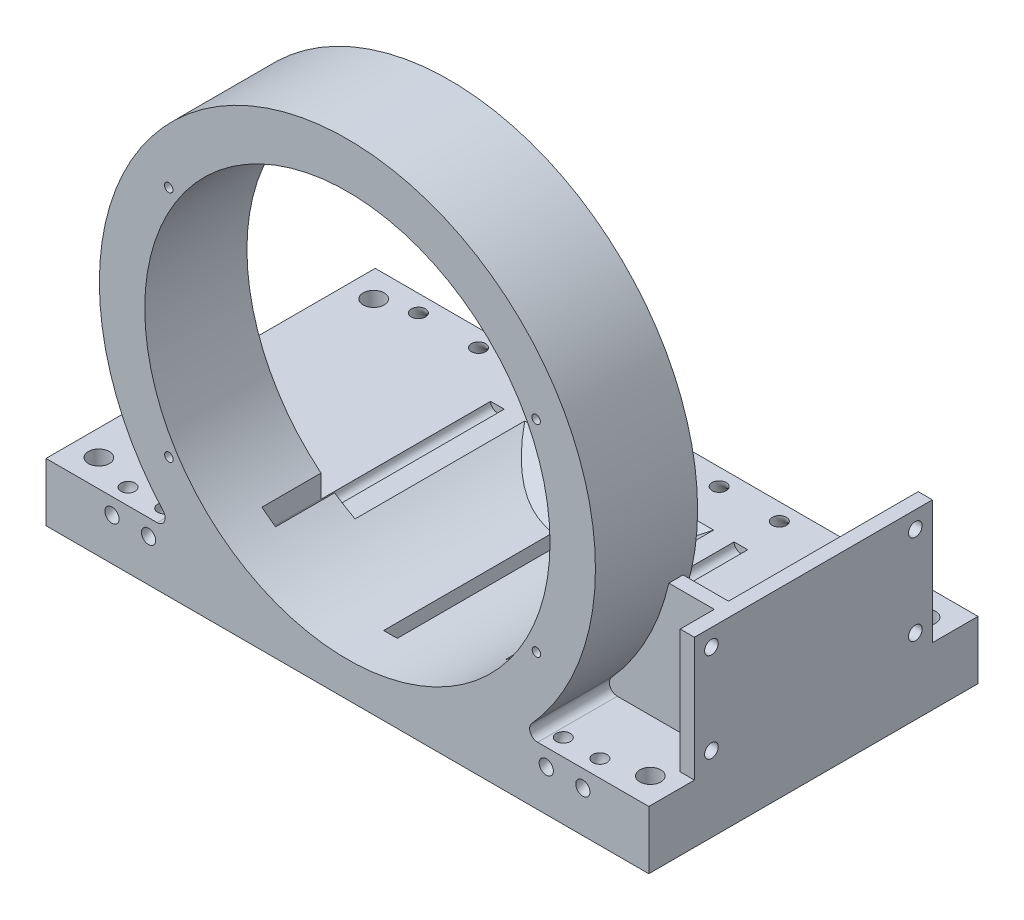
SolidWorks part; units mm, degrees
ref_plane "Front Plane" through (0, 0, 0) normal (0, 0, 1) x (1, 0, 0)
ref_plane "Top Plane" through (0, 0, 0) normal (0, 1, 0) x (1, 0, 0)
ref_plane "Right Plane" through (0, 0, 0) normal (1, 0, 0) x (0, 0, -1)
sketch "Sketch1" plane through (0, 0, 0) normal (0, 0, 1) x (1, 0, 0)
  line L0 (-34.1117, 43.7782) -> (34.1117, 43.7782)
  line L4 (28.448, -40.0843) -> (28.448, -35.2709)
  line L5 (-67.4363, -40.1112) -> (-38.3566, -40.1112)
  line L6 (-67.4363, -40.1112) -> (-67.4363, -53.1541)
  line L7 (-67.4363, -53.1541) -> (67.4363, -53.1541)
  line L8 (67.4363, -40.1112) -> (67.4363, -53.1541)
  line L9 (1.2065, -45.2975) -> (1.2065, -49.1871)
  line L10 (-1.2065, -45.2975) -> (-1.2065, -49.1871)
  line L11 (-45.339, 0) -> (45.339, 0) construction
  line L12 (-28.448, -35.2709) -> (-28.448, -40.0843)
  line L13 (38.3566, -40.1112) -> (67.4363, -40.1112)
  line L14 (26.035, -37.0877) -> (26.035, -40.0843)
  line L15 (0, 45.339) -> (0, -45.339) construction
  line L16 (-26.035, -40.0843) -> (-26.035, -37.0877)
  line L17 (-39.989, 26.0985) -> (-39.9308, -26.0985) construction
  line L18 (42.2197, 22.3102) -> (42.298, -22.7748) construction
  arc A1 (-26.035, -37.1188) -> (-1.2065, -45.3229) centre (0, 0) ccw
  arc A2 (-34.1117, 43.7782) -> (-38.3566, -40.1112) centre (0, 0) ccw
  circle A3 centre (-39.989, 26.0985) radius 0.9525
  arc A4 (38.3566, -40.1112) -> (34.1117, 43.7782) centre (0, 0) ccw
  circle A5 centre (-39.9308, -26.0985) radius 0.9525
  circle A6 centre (42.298, -22.7748) radius 0.9525
  circle A7 centre (42.2197, 22.3102) radius 0.9525
  arc A9 (-1.2065, -49.1871) -> (1.2065, -49.1871) centre (0, -49.1871) ccw
  arc A10 (-28.448, -40.0843) -> (-26.035, -40.0843) centre (-27.2415, -40.0843) ccw
  arc A11 (1.2065, -45.3229) -> (26.035, -37.1188) centre (0, 0) ccw
  arc A12 (26.035, -40.0843) -> (28.448, -40.0843) centre (27.2415, -40.0843) ccw
  arc A13 (28.448, -35.3035) -> (-28.448, -35.3035) centre (0, 0) ccw
  point P8 (0, -45.339)
  point P24 (-39.9599, 0)
  point P25 (42.2589, -0.2323)
  dimension "D1" = 90.678
  dimension "D2" = 10.16
  dimension "D4" = 1.905
  dimension "D5" = 1.905
  dimension "D6" = 1.905
  dimension "D7" = 1.905
  dimension "D10" = 82.296
  dimension "D3" = 2.413
  dimension "D8" = 52.197
  dimension "D9" = 45.085
  dimension "D11" = 82.296
  dimension "D12" = 47.752
  dimension "D13" = 47.752
extrude "Boss-Extrude1" add sketch "Sketch1" along normal blind 22.86 contours L13 A4 L0 A1 A2 L5 L6 L7 L8 region at (-22.9528, 42.1173, 0)
sketch "Sketch2" plane through (0, 0, 0) normal (0, 0, -1) x (-1, 0, 0)
  line L0 (21.1356, -40.1112) -> (26.0353, -40.1112)
  line L1 (-67.4363, -53.1541) -> (67.4363, -53.1541)
  line L2 (-67.4363, -53.1541) -> (-67.4363, -40.1112)
  line L3 (-67.4363, -40.1112) -> (-28.4477, -40.1112)
  line L4 (67.4363, -53.1541) -> (67.4363, -40.1112)
  line L5 (1.2065, -49.1871) -> (1.2065, -45.3229)
  line L6 (28.4477, -40.1112) -> (67.4363, -40.1112)
  line L7 (-1.2065, -45.3229) -> (-1.2065, -49.1871)
  line L8 (-26.0353, -40.1112) -> (-21.1356, -40.1112)
  arc A0 (-21.1356, -40.1112) -> (-1.2065, -45.3229) centre (0, 0) ccw
  arc A1 (-28.4477, -40.1112) -> (-26.0353, -40.1112) centre (-27.2415, -40.0843) ccw
  arc A2 (-1.2065, -49.1871) -> (1.2065, -49.1871) centre (0, -49.1871) ccw
  arc A3 (26.0353, -40.1112) -> (28.4477, -40.1112) centre (27.2415, -40.0843) ccw
  arc A4 (1.2065, -45.3229) -> (21.1356, -40.1112) centre (0, 0) ccw
extrude "Boss-Extrude2" add sketch "Sketch2" along normal blind 50.8 contours L2 L3 A1 L8 A0 L7 A2 L5 A4 L0 A3 L6 L4 L1
sketch "Sketch3" plane through (0, 0, 0) normal (0, 0, -1) x (-1, 0, 0)
  line L0 (-28.448, 40.2554) -> (-28.448, 35.2709)
  line L1 (-28.448, 35.2709) -> (-26.035, 37.0877)
  line L2 (-26.035, 37.0877) -> (-26.035, 40.2554)
  line L3 (28.448, 40.2554) -> (28.448, 35.3035)
  line L4 (28.448, 35.3035) -> (26.0792, 37.0877)
  line L5 (26.0792, 37.0877) -> (26.035, 40.2554)
  line L6 (-25.7175, 36.9294) -> (-25.7175, 40.2554)
  line L7 (-28.7655, 40.2554) -> (-28.7655, 34.6344)
  line L8 (-28.7655, 34.6344) -> (-25.7175, 36.9294)
  line L9 (25.7639, 36.9278) -> (25.7175, 40.251)
  line L10 (28.7655, 34.6668) -> (25.7639, 36.9278)
  line L11 (28.7655, 40.2554) -> (28.7655, 34.6668)
  arc A0 (-26.035, 40.2554) -> (-28.448, 40.2554) centre (-27.2415, 40.2554) ccw
  arc A1 (28.448, 40.2554) -> (26.0355, 40.2217) centre (27.2415, 40.2554) ccw
  arc A2 (28.448, -35.3035) -> (11.7939, 43.7782) centre (0, 0) ccw construction
  arc A3 (-25.7175, 40.2554) -> (-28.7655, 40.2554) centre (-27.2415, 40.2554) ccw
  arc A4 (28.7655, 40.2554) -> (25.7181, 40.2129) centre (27.2415, 40.2554) ccw
  arc M5 (11.7939, 43.7782) -> (28.448, -35.3035) centre (0, 0) cw
  dimension "D1" = 0.3175
extrude "Cut-Extrude1" cut sketch "Sketch3" against normal blind 13.208 contours L3 A1 L5 M5 | L2 A0 L0 L1 region at (27.3142, 38.671, 0) region at (-27.3223, 38.7004, 0)
sketch "Sketch4" plane through (0, 0, 22.86) normal (0, 0, 1) x (1, 0, 0)
  line L0 (-26.035, -40.0843) -> (-26.035, -37.1188)
  line L2 (-28.448, -35.3035) -> (-28.448, -40.0843)
  line L3 (-1.2065, -45.3229) -> (-1.2065, -49.1871)
  line L5 (1.2065, -45.2975) -> (1.2065, -49.1871)
  line L6 (28.448, -40.0843) -> (28.448, -35.3035)
  line L7 (1.1905, -45.3234) -> (1.2065, -45.2975)
  line L8 (26.035, -37.1188) -> (26.035, -40.0843)
  arc A0 (-28.448, -40.0843) -> (-26.035, -40.0843) centre (-27.2415, -40.0843) ccw
  arc A1 (-1.2065, -49.1871) -> (1.2065, -49.1871) centre (0, -49.1871) ccw
  arc A2 (26.035, -40.0843) -> (28.448, -40.0843) centre (27.2415, -40.0843) ccw
  arc A3 (-28.448, -35.3035) -> (-26.035, -37.1188) centre (0, 0) ccw
  arc A4 (-1.2065, -45.3229) -> (1.2065, -45.3229) centre (0, 0) ccw
  arc A5 (26.035, -37.1188) -> (28.448, -35.3035) centre (0, 0) ccw
  line M14 (28.448, -35.3035) -> (28.448, -40.0843)
  arc M15 (28.448, -40.0843) -> (26.035, -40.0843) centre (27.2415, -40.0843) cw
  line M16 (26.035, -40.0843) -> (26.035, -37.1188)
  line M18 (1.2065, -45.3229) -> (1.2065, -49.1871)
  arc M19 (1.2065, -49.1871) -> (-1.2065, -49.1871) centre (0, -49.1871) cw
  line M20 (-1.2065, -49.1871) -> (-1.2065, -45.3229)
  line M22 (-26.035, -37.1188) -> (-26.035, -40.0843)
  arc M23 (-26.035, -40.0843) -> (-28.448, -40.0843) centre (-27.2415, -40.0843) cw
  line M24 (-28.448, -40.0843) -> (-28.448, -35.3035)
extrude "Boss-Extrude3" add sketch "Sketch4" against normal blind 9.652 contours A3 M24 M23 M22 | A4 M20 M19 M18 | A5 M16 M15 M14 region at (-27.3175, -38.611, 22.86) region at (0, -47.7417, 22.86) region at (27.3175, -38.611, 22.86)
sketch "Sketch6" plane through (67.4363, 0, 0) normal (1, 0, 0) x (0, 0, -1)
  line L2 (20.8189, -46.8236) -> (20.8189, -53.1541)
  line L3 (50.8, -40.1112) -> (50.8, -45.3976)
  line L5 (-22.86, -53.1541) -> (50.8, -53.1541) construction
  line L6 (20.8189, -53.1541) -> (50.8, -53.1541)
  line L9 (50.8, -53.1541) -> (50.8, -45.3976)
  line L10 (50.8, -53.1541) -> (50.8, -40.1112) construction
  line L12 (50.8, -40.1112) -> (37.9477, -40.1112)
  line L13 (-22.86, -40.1112) -> (50.8, -40.1112) construction
  line L14 (37.9477, -40.1112) -> (20.8189, -46.8236)
extrude "Boss-Extrude5" add sketch "Sketch6" against normal blind 116.84 contours L14 L2 L6 L9 L3 L12
sketch "Sketch7" plane through (0, -53.1541, 0) normal (0, -1, 0) x (1, 0, 0)
  line L0 (-61.6911, -44.7061) -> (-61.6911, 16.7661) construction
  line L1 (0, -13.97) -> (-61.6911, 16.7661)
  line L2 (-61.6911, 16.7661) -> (61.6911, -44.7061)
  line L3 (0, -13.97) -> (-61.6911, -13.97) construction
  line L4 (0, 22.86) -> (0, -50.8) construction
  line L5 (-67.4363, 22.86) -> (67.4363, 22.86) construction
  line L6 (67.4363, -50.8) -> (-67.4363, -50.8) construction
  circle A0 centre (-61.6911, 16.7661) radius 2.3495
  circle A1 centre (61.6911, -44.7061) radius 2.3495
  circle A2 centre (-61.6911, -44.7061) radius 2.3495
  circle A3 centre (61.6911, 16.7661) radius 2.3495
  dimension "D3" = 4.699
  dimension "D4" = 4.699
  dimension "D1" = 68.9238
  dimension "D2" = 137.8477
  dimension "D5" = 61.4723
extrude "Cut-Extrude2" cut sketch "Sketch7" against normal blind 25.4 contours A0 | A2 | A1 | A3 region at (-63.9134, -53.1541, 17.2891) region at (-61.6911, -53.1541, -44.7061)
sketch "Sketch8" plane through (0, -40.1112, 0) normal (0, 1, 0) x (1, 0, 0)
  line L0 (-67.4363, 50.8) -> (67.4363, 50.8)
  line L1 (-67.4363, 50.8) -> (-67.4363, 46.99)
  line L2 (-67.4363, -22.86) -> (-67.4363, 50.8) construction
  line L3 (-67.4363, 46.99) -> (67.4363, 46.99) construction
  line L4 (67.4363, -22.86) -> (67.4363, 50.8) construction
  line L5 (-67.4363, -22.86) -> (-67.4363, -17.78)
  line L6 (-67.4363, -17.78) -> (67.4363, -17.78) construction
  line L7 (-0.1263, 46.99) -> (0, -17.78) construction
  circle A0 centre (-53.9743, 46.99) radius 1.5875
  circle A1 centre (-40.5123, 46.99) radius 1.5875
  circle A2 centre (-27.0503, 46.99) radius 1.5875
  circle A3 centre (-13.5883, 46.99) radius 1.5875
  circle A4 centre (-0.1263, 46.99) radius 1.5875
  circle A5 centre (13.3357, 46.99) radius 1.5875
  circle A6 centre (26.7977, 46.99) radius 1.5875
  circle A7 centre (40.2597, 46.99) radius 1.5875
  circle A8 centre (53.7217, 46.99) radius 1.5875
  circle A9 centre (53.7217, -17.78) radius 1.5875
  circle A10 centre (44.6271, -17.78) radius 1.5875
  circle A11 centre (-53.7213, -17.9895) radius 1.5875
  circle A12 centre (-44.6267, -17.9541) radius 1.5875
  dimension "D1" = 3.175
  dimension "D6" = 3.175
  dimension "D7" = 3.175
  dimension "D2" = 3.81
  dimension "D3" = 13.462
  dimension "D5" = 5.08
  dimension "D4" = 9
revolve "Cut-Revolve1" cut sketch "Sketch8" angle 360 about L0 region at (-53.9743, -40.1112, -46.99) region at (-40.5123, -40.1112, -46.99) region at (-27.0503, -40.1112, -46.99) region at (-13.5883, -40.1112, -46.99) region at (-0.1263, -40.1112, -46.99) region at (13.3357, -40.1112, -46.99) region at (26.7977, -40.1112, -46.99) region at (40.2597, -40.1112, -46.99) region at (53.7217, -40.1112, -46.99)
sketch "Sketch9" plane through (0, -40.1112, 0) normal (0, 1, 0) x (1, 0, 0)
  line L0 (-67.4363, -22.86) -> (-67.4363, -19.05)
  line L1 (-67.4363, -22.86) -> (-67.4363, 50.8) construction
  line L2 (-67.4363, -19.05) -> (67.4363, -19.05) construction
  line L3 (67.4363, -22.86) -> (67.4363, 50.8) construction
  line L4 (0, -19.05) -> (-0.1263, 45.4025)
  circle A0 centre (44.4978, -19.05) radius 1.5875
  circle A1 centre (52.6808, -19.05) radius 1.5875
  circle A2 centre (-0.1263, 46.99) radius 1.5875 construction
  circle A3 centre (-52.6804, -19.2565) radius 1.5875
  circle A4 centre (-44.4975, -19.2244) radius 1.5875
  dimension "D2" = 3.175
  dimension "D3" = 3.175
  dimension "D1" = 3.81
revolve "Cut-Revolve2" cut sketch "Sketch9" angle 360 about axis through (0, -40.1112, 22.86) along (1, 0, 0) region at (-52.6804, -40.1112, 18.4698) region at (52.6808, -40.1112, 18.3762) region at (52.6808, -40.1112, 19.7238) region at (44.4978, -40.1112, 18.3762) region at (44.4978, -40.1112, 19.7238) region at (-44.4975, -40.1112, 18.4555) region at (-44.4975, -40.1112, 19.805) region at (-52.6804, -40.1112, 19.8201)
fillet "Fillet1" radius 1.778 2 edges at (-38.3566, -40.1112, 11.43) (38.3566, -40.1112, 11.43)
sketch "Sketch11" plane through (0, 0, 0) normal (0, 0, -1) x (-1, 0, 0)
  line L1 (28.448, -35.3035) -> (28.448, -40.0843) construction
  line L2 (28.4477, -40.1112) -> (42.5584, -40.1112) construction
  line L3 (34.1117, 43.7782) -> (11.7939, 43.7782) construction
  line L5 (-26.035, 40.2554) -> (-26.035, 37.1188) construction
  line L6 (-11.7939, 43.7782) -> (-34.1117, 43.7782) construction
  line L7 (-42.5584, -40.1112) -> (-28.4477, -40.1112) construction
  line L8 (-28.448, -40.0843) -> (-28.448, -35.3035) construction
  line L9 (-28.448, 35.3035) -> (-28.448, 40.2554) construction
  line L11 (28.448, -35.3035) -> (28.448, -40.0843)
  line L12 (28.4477, -40.1112) -> (42.5584, -40.1112)
  line L13 (34.1117, 43.7782) -> (11.7939, 43.7782)
  line L15 (-26.035, 40.2554) -> (-26.035, 37.1188)
  line L16 (-11.7939, 43.7782) -> (-34.1117, 43.7782)
  line L17 (-42.5584, -40.1112) -> (-28.4477, -40.1112)
  line L18 (-28.448, -40.0843) -> (-28.448, -35.3035)
  line L19 (-28.448, 35.3035) -> (-28.448, 40.2554)
  line L20 (-28.829, 40.2554) -> (-28.829, 34.9931)
  line L21 (-25.654, 40.2554) -> (-25.654, 37.3831)
  line L22 (-11.7939, 43.7782) -> (11.7939, 43.7782)
  line L23 (0, 43.7782) -> (0, 33.6339)
  line L24 (-25.7175, -40.0843) -> (-25.7175, -36.9533)
  line L25 (-28.7655, -34.6335) -> (-28.7655, -40.0843)
  line L26 (-26.0353, -40.1112) -> (-21.1356, -40.1112)
  line L27 (-26.035, -37.1188) -> (-26.035, -40.0843)
  line L28 (-26.0353, -40.1112) -> (-21.1356, -40.1112)
  line L29 (-26.035, -37.1188) -> (-26.035, -40.0843)
  line L30 (-28.448, -35.3035) -> (-28.448, -40.0843)
  line L31 (-26.035, -40.0843) -> (-26.035, -37.1188)
  line L32 (-28.448, -35.3035) -> (-28.448, -40.0843)
  line L33 (-26.035, -40.0843) -> (-26.035, -37.1188)
  line L34 (-1.2065, -45.3229) -> (-1.2065, -49.1871)
  line L35 (1.2065, -49.1871) -> (1.2065, -45.3229)
  line L36 (-1.2065, -45.3229) -> (-1.2065, -49.1871)
  line L37 (1.2065, -49.1871) -> (1.2065, -45.3229)
  line L38 (1.524, -49.1871) -> (1.524, -44.9957)
  line L39 (-1.524, -44.9957) -> (-1.524, -49.1871)
  line L40 (1.524, -44.9957) -> (1.524, -49.1871)
  line L41 (-1.524, -49.1871) -> (-1.524, -44.9957)
  line L42 (-1.2065, -49.1871) -> (-1.2065, -45.3229)
  line L43 (1.2065, -45.3229) -> (1.2065, -49.1871)
  line L44 (26.035, -40.0843) -> (26.035, -37.1188)
  line L45 (28.448, -35.3035) -> (28.448, -40.0843)
  line L46 (26.035, -37.1188) -> (26.035, -40.0843)
  line L47 (26.0353, -40.1112) -> (21.1356, -40.1112)
  line L48 (28.7655, -34.6335) -> (28.7655, -40.0843)
  line L49 (25.7175, -40.0843) -> (25.7175, -36.9533)
  line L50 (25.654, 40.2554) -> (25.654, 37.3831)
  line L51 (28.829, 40.2554) -> (28.829, 34.9931)
  line L53 (28.448, -40.0843) -> (28.448, -35.3035)
  line L54 (42.5584, -40.1112) -> (28.4477, -40.1112)
  line L55 (11.7939, 43.7782) -> (34.1117, 43.7782)
  line L62 (28.448, 40.2554) -> (28.448, 35.3035)
  line L63 (28.448, -35.3035) -> (28.448, -40.0843)
  line L64 (28.4477, -40.1112) -> (42.5584, -40.1112)
  line L65 (34.1117, 43.7782) -> (11.7939, 43.7782)
  line L66 (26.0792, 37.0877) -> (26.035, 40.2554)
  line L68 (28.448, -35.3035) -> (28.448, -40.0843)
  line L69 (28.4477, -40.1112) -> (42.5584, -40.1112)
  line L70 (34.1117, 43.7782) -> (11.7939, 43.7782)
  arc A0 (28.448, -35.3035) -> (28.448, 35.3035) centre (0, 0) ccw construction
  arc A1 (28.4477, -40.1112) -> (28.448, -40.0843) centre (27.2415, -40.0843) ccw construction
  arc A2 (41.2373, -37.1433) -> (42.5584, -40.1112) centre (42.5584, -38.3332) ccw construction
  arc A3 (41.2373, -37.1433) -> (34.1117, 43.7782) centre (0, 0) ccw construction
  arc A4 (26.0792, 37.0877) -> (11.7939, 43.7782) centre (0, 0) ccw construction
  arc A5 (28.448, 40.2554) -> (26.035, 40.2554) centre (27.2415, 40.2554) ccw construction
  arc A6 (-26.035, 40.2554) -> (-28.448, 40.2554) centre (-27.2415, 40.2554) ccw construction
  arc A7 (-11.7939, 43.7782) -> (-26.035, 37.1188) centre (0, 0) ccw construction
  arc A8 (-34.1117, 43.7782) -> (-41.2373, -37.1433) centre (0, 0) ccw construction
  arc A9 (-42.5584, -40.1112) -> (-41.2373, -37.1433) centre (-42.5584, -38.3332) ccw construction
  arc A10 (-28.448, -40.0843) -> (-28.4477, -40.1112) centre (-27.2415, -40.0843) ccw construction
  arc A11 (-28.448, 35.3035) -> (-28.448, -35.3035) centre (0, 0) ccw construction
  arc A12 (28.448, -35.3035) -> (28.448, 35.3035) centre (0, 0) ccw
  arc A13 (28.4477, -40.1112) -> (28.448, -40.0843) centre (27.2415, -40.0843) ccw
  arc A14 (41.2373, -37.1433) -> (42.5584, -40.1112) centre (42.5584, -38.3332) ccw
  arc A15 (41.2373, -37.1433) -> (34.1117, 43.7782) centre (0, 0) ccw
  arc A16 (26.0792, 37.0877) -> (11.7939, 43.7782) centre (0, 0) ccw
  arc A18 (-26.035, 40.2554) -> (-28.448, 40.2554) centre (-27.2415, 40.2554) ccw
  arc A19 (-11.7939, 43.7782) -> (-26.035, 37.1188) centre (0, 0) ccw
  arc A20 (-34.1117, 43.7782) -> (-41.2373, -37.1433) centre (0, 0) ccw
  arc A21 (-42.5584, -40.1112) -> (-41.2373, -37.1433) centre (-42.5584, -38.3332) ccw
  arc A22 (-28.448, -40.0843) -> (-28.4477, -40.1112) centre (-27.2415, -40.0843) ccw
  arc A23 (-28.448, 35.3035) -> (-28.448, -35.3035) centre (0, 0) ccw
  circle A24 centre (-27.2415, 40.2554) radius 1.5875
  arc A25 (-28.7655, -40.0843) -> (-25.7175, -40.0843) centre (-27.2415, -40.0843) ccw
  arc A26 (-28.7655, -34.6335) -> (-25.7175, -36.9533) centre (0, 0) ccw
  arc A27 (-26.0353, -40.1112) -> (-26.035, -40.0843) centre (-27.2415, -40.0843) ccw
  arc A28 (-26.035, -37.1188) -> (-21.1356, -40.1112) centre (0, 0) ccw
  arc A29 (-26.0353, -40.1112) -> (-26.035, -40.0843) centre (-27.2415, -40.0843) ccw
  arc A30 (-26.035, -37.1188) -> (-21.1356, -40.1112) centre (0, 0) ccw
  arc A31 (-28.448, -35.3035) -> (-26.035, -37.1188) centre (0, 0) ccw
  arc A32 (-28.448, -40.0843) -> (-26.035, -40.0843) centre (-27.2415, -40.0843) ccw
  arc A33 (-28.448, -35.3035) -> (-26.035, -37.1188) centre (0, 0) ccw
  arc A34 (-28.448, -40.0843) -> (-26.035, -40.0843) centre (-27.2415, -40.0843) ccw
  arc A35 (-1.2065, -45.3229) -> (1.2065, -45.3229) centre (0, 0) ccw
  arc A36 (-1.2065, -49.1871) -> (1.2065, -49.1871) centre (0, -49.1871) ccw
  arc A37 (-1.2065, -45.3229) -> (1.2065, -45.3229) centre (0, 0) ccw
  arc A38 (-1.2065, -49.1871) -> (1.2065, -49.1871) centre (0, -49.1871) ccw
  arc A39 (-1.524, -49.1871) -> (1.524, -49.1871) centre (0, -49.1871) ccw
  arc A40 (-1.524, -44.9957) -> (1.524, -44.9957) centre (0, 0) ccw
  arc A41 (28.448, -40.0843) -> (26.035, -40.0843) centre (27.2415, -40.0843) cw
  arc A42 (28.448, -35.3035) -> (26.035, -37.1188) centre (0, 0) cw
  arc A43 (26.035, -37.1188) -> (21.1356, -40.1112) centre (0, 0) cw
  arc A44 (26.0353, -40.1112) -> (26.035, -40.0843) centre (27.2415, -40.0843) cw
  arc A45 (28.7655, -34.6335) -> (25.7175, -36.9533) centre (0, 0) cw
  arc A46 (28.7655, -40.0843) -> (25.7175, -40.0843) centre (27.2415, -40.0843) cw
  arc A48 (28.448, 35.3035) -> (28.448, -35.3035) centre (0, 0) cw
  arc A49 (28.448, -40.0843) -> (28.4477, -40.1112) centre (27.2415, -40.0843) cw
  arc A50 (42.5584, -40.1112) -> (41.2373, -37.1433) centre (42.5584, -38.3332) cw
  arc A51 (34.1117, 43.7782) -> (41.2373, -37.1433) centre (0, 0) cw
  arc A52 (11.7939, 43.7782) -> (26.035, 37.1188) centre (0, 0) cw
  arc A54 (28.829, 40.2554) -> (25.654, 40.2554) centre (27.2415, 40.2554) ccw
  circle A55 centre (0, 0) radius 45.339
  arc A60 (28.448, -35.3035) -> (28.448, 35.3035) centre (0, 0) ccw
  arc A61 (28.4477, -40.1112) -> (28.448, -40.0843) centre (27.2415, -40.0843) ccw
  arc A62 (41.2373, -37.1433) -> (42.5584, -40.1112) centre (42.5584, -38.3332) ccw
  arc A63 (41.2373, -37.1433) -> (34.1117, 43.7782) centre (0, 0) ccw
  arc A64 (26.0792, 37.0877) -> (11.7939, 43.7782) centre (0, 0) ccw
  arc A65 (28.448, 40.2554) -> (26.035, 40.2554) centre (27.2415, 40.2554) ccw
  arc A66 (28.448, -35.3035) -> (28.448, 35.3035) centre (0, 0) ccw
  arc A67 (28.4477, -40.1112) -> (28.448, -40.0843) centre (27.2415, -40.0843) ccw
  arc A68 (41.2373, -37.1433) -> (42.5584, -40.1112) centre (42.5584, -38.3332) ccw
  arc A69 (41.2373, -37.1433) -> (34.1117, 43.7782) centre (0, 0) ccw
  arc A70 (26.0792, 37.0877) -> (11.7939, 43.7782) centre (0, 0) ccw
  arc M27 (-28.448, 40.2554) -> (-26.035, 40.2554) centre (-27.2415, 40.2554) cw
  line M28 (-26.035, 40.2554) -> (-26.035, 37.1188)
  arc M29 (-26.035, 37.1188) -> (-11.7939, 43.7782) centre (0, 0) cw
  arc M34 (-28.4477, -40.1112) -> (-28.448, -40.0843) centre (-27.2415, -40.0843) cw
  line M35 (-28.448, -40.0843) -> (-28.448, -35.3035)
  arc M36 (-28.448, -35.3035) -> (-28.448, 35.3035) centre (0, 0) cw
  line M37 (-28.448, 35.3035) -> (-28.448, 40.2554)
  dimension "D1" = 3.175
  dimension "D2" = 0
  dimension "D3" = 0
  dimension "D4" = 0
  dimension "D5" = 0.3175
  dimension "D6" = 0.3175
  dimension "D7" = 0
extrude "Cut-Extrude3" cut sketch "Sketch11" against normal up to surface (13.208 mm away) contours A24 L20 M36 M37 | A24 L19 M27 M28 | A24 L15 L21 M29 | A34 L17 A25 L28 | A30 L29 A29 L28 A25 L24 | L25 A25 L17 M34 M35 M36 | A40 L39 A39 L38 A38 L36 A37 L37 | A46 L48 A12 L11 A13 L12 | A46 L12 A41 L47 | A46 L47 A41 L44 A43 L49 | A16 region at (-28.6081, -37.6424, 0) region at (-25.8783, -38.6696, 0) region at (-28.6065, -40.1452, 0) region at (-28.6866, 35.2073, 0) region at (-1.462, -47.2502, 0) region at (25.837, 38.4116, 0) region at (27.2415, -41.5744, 0) region at (25.8783, -38.6696, 0) region at (25.7909, 39.7197, 0) region at (28.6081, -37.6424, 0) region at (28.6466, 37.3546, 0) up to face at (-27.2453, -38.4544, 13.208)
sketch "Sketch12" plane through (0, 0, 0) normal (0, 0, 1) x (1, 0, 0)
  line L0 (28.7653, -40.1112) -> (28.4477, -40.1112) construction
  line L1 (26.0353, -40.1112) -> (25.7177, -40.1112) construction
  line L2 (1.2065, -45.3229) -> (1.2065, -49.1871) construction
  line L3 (-1.2065, -49.1871) -> (-1.2065, -45.3229) construction
  line L4 (-1.524, -45.3134) -> (-1.524, -49.1871) construction
  line L5 (1.524, -49.1871) -> (1.524, -45.3134) construction
  line L6 (-25.7177, -40.1112) -> (-26.0353, -40.1112) construction
  line L7 (-28.4477, -40.1112) -> (-28.7653, -40.1112) construction
  line L8 (28.7653, -40.1112) -> (28.4477, -40.1112)
  line L9 (26.0353, -40.1112) -> (25.7177, -40.1112)
  line L10 (1.2065, -45.3229) -> (1.2065, -49.1871)
  line L11 (-1.2065, -49.1871) -> (-1.2065, -45.3229)
  line L12 (-1.524, -45.3134) -> (-1.524, -49.1871)
  line L13 (1.524, -49.1871) -> (1.524, -45.3134)
  line L14 (-25.7177, -40.1112) -> (-26.0353, -40.1112)
  line L15 (-28.4477, -40.1112) -> (-28.7653, -40.1112)
  line L16 (-28.4477, -40.1112) -> (-26.0353, -40.1112)
  line L17 (-1.2065, -45.3229) -> (1.2065, -45.3229)
  line L18 (26.0353, -40.1112) -> (28.4477, -40.1112)
  line L20 (1.524, -45.3134) -> (-1.524, -45.3134)
  line L21 (1.524, -45.3134) -> (1.524, -39.544)
  line L22 (1.524, -39.544) -> (-1.524, -39.544)
  line L23 (-1.524, -45.3134) -> (-1.524, -39.544)
  arc A0 (26.0353, -40.1112) -> (28.4477, -40.1112) centre (27.2415, -40.0843) ccw construction
  arc A1 (25.7177, -40.1112) -> (28.7653, -40.1112) centre (27.2415, -40.0843) ccw construction
  arc A2 (1.2065, -45.3229) -> (1.524, -45.3134) centre (0, 0) ccw construction
  arc A3 (-1.2065, -49.1871) -> (1.2065, -49.1871) centre (0, -49.1871) ccw construction
  arc A4 (-1.524, -45.3134) -> (-1.2065, -45.3229) centre (0, 0) ccw construction
  arc A5 (-1.524, -49.1871) -> (1.524, -49.1871) centre (0, -49.1871) ccw construction
  arc A6 (-28.4477, -40.1112) -> (-26.0353, -40.1112) centre (-27.2415, -40.0843) ccw construction
  arc A7 (-28.7653, -40.1112) -> (-25.7177, -40.1112) centre (-27.2415, -40.0843) ccw construction
  arc A8 (26.0353, -40.1112) -> (28.4477, -40.1112) centre (27.2415, -40.0843) ccw
  arc A9 (25.7177, -40.1112) -> (28.7653, -40.1112) centre (27.2415, -40.0843) ccw
  arc A10 (1.2065, -45.3229) -> (1.524, -45.3134) centre (0, 0) ccw
  arc A11 (-1.2065, -49.1871) -> (1.2065, -49.1871) centre (0, -49.1871) ccw
  arc A12 (-1.524, -45.3134) -> (-1.2065, -45.3229) centre (0, 0) ccw
  arc A13 (-1.524, -49.1871) -> (1.524, -49.1871) centre (0, -49.1871) ccw
  arc A14 (-28.4477, -40.1112) -> (-26.0353, -40.1112) centre (-27.2415, -40.0843) ccw
  arc A15 (-28.7653, -40.1112) -> (-25.7177, -40.1112) centre (-27.2415, -40.0843) ccw
  arc M1 (1.524, -45.3134) -> (1.2065, -45.3229) centre (0, 0) cw
  line M2 (1.2065, -45.3229) -> (1.2065, -49.1871)
  arc M3 (1.2065, -49.1871) -> (-1.2065, -49.1871) centre (0, -49.1871) cw
  line M4 (-1.2065, -49.1871) -> (-1.2065, -45.3229)
  arc M5 (-1.2065, -45.3229) -> (-1.524, -45.3134) centre (0, 0) cw
  line M6 (-1.524, -45.3134) -> (-1.524, -49.1871)
  arc M7 (-1.524, -49.1871) -> (1.524, -49.1871) centre (0, -49.1871) ccw
  line M8 (1.524, -49.1871) -> (1.524, -45.3134)
extrude "Cut-Extrude4" cut sketch "Sketch12" against normal up to vertex (37.9477 mm away) contours L18 A8 | L9 A9 L8 A8 | M8 M1 M2 M3 M4 M5 M6 M7 | L17 M4 M3 M2 | L15 A15 L14 A14 | L16 A14 | L20 L17 M1 M5 | L23 L20 L21 L22 region at (27.2415, -41.5744, 0) region at (27.2415, -40.6109, 0) region at (1.3671, -45.3804, 0) region at (0, -47.7363, 0) region at (0, -45.318, 0) region at (0, -42.4287, 0) region at (-27.2415, -41.5744, 0) region at (-27.2415, -40.6109, 0) up to point (-21.1356, -40.1112, -37.9477)
sketch "Sketch13" plane through (0, 0, 0) normal (0, 0, -1) x (-1, 0, 0)
  line L0 (-34.1117, 43.7782) -> (34.1117, 43.7782)
  circle A0 centre (0, 0) radius 45.339
  circle A1 centre (0, 0) radius 55.499
  line M10 (-11.7939, 43.7782) -> (-34.1117, 43.7782)
extrude "Boss-Extrude6" add sketch "Sketch13" against normal up to surface (22.86 mm away) contours L0 A1 A0 M10 region at (0, 48.706, 0) up to face at (-51.0929, -43.7147, 22.86)
sketch "Sketch14" plane through (67.4363, 0, 0) normal (1, 0, 0) x (0, 0, -1)
  line L0 (13.97, -40.1112) -> (13.97, 13.5172)
  line L1 (-8.8392, -16.2352) -> (36.7792, -16.2352)
  line L2 (-8.8392, -16.2352) -> (-8.8392, -36.3012)
  line L3 (-8.8392, -36.3012) -> (36.7792, -36.3012)
  line L4 (36.7792, -16.2352) -> (36.7792, -36.3012)
  line L5 (-22.86, -40.1112) -> (50.8, -40.1112) construction
  line L14 (-12.6492, -12.4252) -> (40.5892, -12.4252)
  line L15 (40.5892, -12.4252) -> (40.5892, -40.1112)
  line L16 (-12.6492, -40.1112) -> (40.5892, -40.1112)
  line L17 (-12.6492, -12.4252) -> (-12.6492, -40.1112)
  circle A0 centre (-8.8392, -16.2352) radius 1.524
  circle A1 centre (36.7792, -36.3012) radius 1.524
  circle A2 centre (-8.8392, -36.3012) radius 1.524
  circle A3 centre (36.7792, -16.2352) radius 1.524
  line M8 (50.8, -40.1112) -> (-22.86, -40.1112)
  dimension "D1" = 3.048
  dimension "D2" = 3.048
  dimension "D3" = 3.048
  dimension "D4" = 3.048
  dimension "D5" = 20.066
  dimension "D6" = 45.6184
  dimension "D7" = 22.8092
  dimension "D8" = 3.81
extrude "Boss-Extrude8" add sketch "Sketch14" against normal blind 3.175 contours A3 L4 A1 L3 L0 L15 L14 L1 M8 | A2 L2 A0 L1 L0 L14 L17 L3 M8 | A2 L3 L0 L1 A0 L2 | A3 L1 L0 L3 A1 L4 region at (67.4363, -39.7271, -0.6604) region at (67.4363, -38.2062, -14.3541) region at (67.4363, -26.2682, -2.6518) region at (67.4363, -26.2682, -25.2882)
ref_plane "Plane3" through (0, 0, 5.0292) normal (0, 0, 1) x (1, 0, 0)
ref_plane "Plane4" through (0, 0, -32.9692) normal (0, 0, -1) x (-1, 0, 0)
sketch "Sketch16" plane through (0, 0, 5.0292) normal (0, 0, 1) x (1, 0, 0)
  line L0 (67.4363, -40.1112) -> (67.4363, -12.4252) construction
  line L1 (67.4363, -12.4252) -> (64.2613, -12.4252) construction
  line L2 (64.2613, -12.4252) -> (64.2613, -40.1112) construction
  line L3 (64.2613, -40.1112) -> (67.4363, -40.1112) construction
  line L4 (-42.5584, -40.1112) -> (-67.4363, -40.1112) construction
  line L5 (-67.4363, -40.1112) -> (-67.4363, -53.1541) construction
  line L6 (-67.4363, -53.1541) -> (67.4363, -53.1541) construction
  line L7 (67.4363, -53.1541) -> (67.4363, -40.1112) construction
  line L8 (67.4363, -40.1112) -> (42.5584, -40.1112) construction
  line L9 (67.4363, -40.1112) -> (67.4363, -12.4252)
  line L10 (67.4363, -12.4252) -> (64.2613, -12.4252)
  line L11 (64.2613, -12.4252) -> (64.2613, -40.1112)
  line L12 (64.2613, -40.1112) -> (67.4363, -40.1112)
  line L13 (-42.5584, -40.1112) -> (-67.4363, -40.1112)
  line L14 (-67.4363, -40.1112) -> (-67.4363, -53.1541)
  line L15 (-67.4363, -53.1541) -> (67.4363, -53.1541)
  line L16 (67.4363, -53.1541) -> (67.4363, -40.1112)
  line L17 (67.4363, -40.1112) -> (42.5584, -40.1112)
  line L18 (64.2613, -12.4252) -> (54.0902, -12.4252)
  arc A0 (41.2373, -37.1433) -> (42.5584, -40.1112) centre (42.5584, -38.3332) ccw construction
  arc A1 (41.2373, -37.1433) -> (-41.2373, -37.1433) centre (0, 0) ccw construction
  arc A2 (-42.5584, -40.1112) -> (-41.2373, -37.1433) centre (-42.5584, -38.3332) ccw construction
  arc A3 (41.2373, -37.1433) -> (42.5584, -40.1112) centre (42.5584, -38.3332) ccw
  arc A4 (41.2373, -37.1433) -> (-41.2373, -37.1433) centre (0, 0) ccw
  arc A5 (-42.5584, -40.1112) -> (-41.2373, -37.1433) centre (-42.5584, -38.3332) ccw
extrude "Boss-Extrude9" add sketch "Sketch16" against normal blind 3.175 contours A4 A3 L17 L11 L18 region at (55.6406, -28.3627, 5.0292)
sketch "Sketch17" plane through (0, 0, -32.9692) normal (0, 0, -1) x (-1, 0, 0)
  line L0 (67.4363, -40.1112) -> (-67.4363, -40.1112) construction
  line L1 (-67.4363, -40.1112) -> (-67.4363, -53.1541) construction
  line L2 (-67.4363, -53.1541) -> (67.4363, -53.1541) construction
  line L3 (67.4363, -53.1541) -> (67.4363, -40.1112) construction
  line L4 (-67.4363, -12.4252) -> (-67.4363, -40.1112) construction
  line L5 (-67.4363, -40.1112) -> (-64.2613, -40.1112) construction
  line L6 (-64.2613, -40.1112) -> (-64.2613, -12.4252) construction
  line L7 (-64.2613, -12.4252) -> (-67.4363, -12.4252) construction
  line L8 (67.4363, -40.1112) -> (-67.4363, -40.1112)
  line L9 (-67.4363, -40.1112) -> (-67.4363, -53.1541)
  line L10 (-67.4363, -53.1541) -> (67.4363, -53.1541)
  line L11 (67.4363, -53.1541) -> (67.4363, -40.1112)
  line L12 (-67.4363, -12.4252) -> (-67.4363, -40.1112)
  line L13 (-67.4363, -40.1112) -> (-64.2613, -40.1112)
  line L14 (-64.2613, -40.1112) -> (-64.2613, -12.4252)
  line L15 (-64.2613, -12.4252) -> (-67.4363, -12.4252)
  line L16 (-64.2613, -12.4252) -> (-43.8863, -40.1112)
extrude "Boss-Extrude10" add sketch "Sketch17" against normal blind 3.175 contours L16 L14 L8 region at (57.4696, -30.8825, -32.9692)
sketch "Sketch18" plane through (0, 0, 0) normal (0, 0, -1) x (-1, 0, 0)
  line L0 (-45.339, -0.0411) -> (45.339, -0.0411)
  line L1 (-1.524, 45.2312) -> (-1.524, 49.1049)
  line L2 (1.524, -49.1871) -> (1.524, -45.3134)
  line L3 (-1.524, -45.3134) -> (-1.524, -49.1871)
  line L4 (1.524, -49.1871) -> (1.524, -45.3134)
  line L5 (-1.524, -45.3134) -> (-1.524, -49.1871)
  line L6 (1.524, 49.1049) -> (1.524, 45.2312)
  line L9 (-1.524, 45.2312) -> (-1.524, 41.2188)
  line L10 (-1.524, 41.2188) -> (1.524, 41.2188)
  line L11 (1.524, 45.2312) -> (1.524, 41.2188)
  arc A0 (-28.829, 34.9931) -> (-28.7655, -35.0453) centre (0, 0) ccw construction
  arc A1 (28.7655, -35.0453) -> (28.829, 34.9931) centre (0, 0) ccw construction
  arc A2 (-1.524, -45.3134) -> (1.524, -45.3134) centre (0, 0) ccw
  arc A3 (-1.524, -49.1871) -> (1.524, -49.1871) centre (0, -49.1871) ccw
  arc A4 (-1.524, -45.3134) -> (1.524, -45.3134) centre (0, 0) ccw
  arc A5 (-1.524, -49.1871) -> (1.524, -49.1871) centre (0, -49.1871) ccw
  arc A6 (-1.524, 49.1049) -> (1.524, 49.1049) centre (0, 49.1049) cw
  arc M15 (-25.654, 37.3831) -> (25.654, 37.3831) centre (0, 0) cw
  dimension "D1" = 0
extrude "Cut-Extrude5" cut sketch "Sketch18" against normal up to surface (13.208 mm away) contours L11 L6 L1 L9 L10 M15 | A6 L1 L6 M15 region at (0, 43.2747, 0) region at (0, 47.8278, 0) up to face at (0, -47.6376, 13.208)
